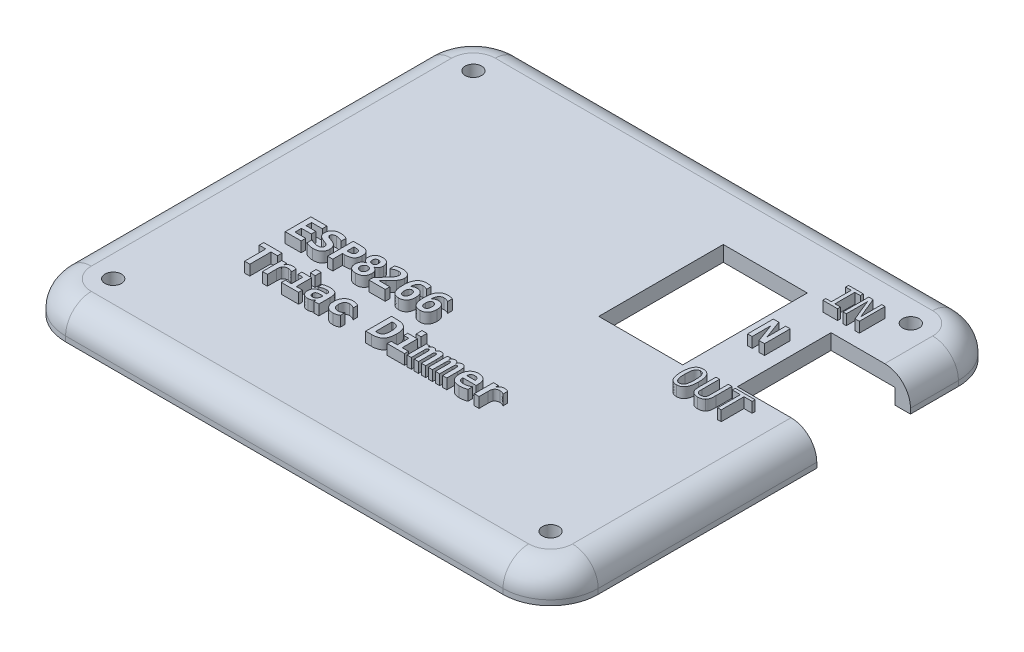
SolidWorks part; units mm, degrees
ref_plane "Front Plane" through (0, 0, 0) normal (0, 0, 1) x (1, 0, 0)
ref_plane "Top Plane" through (0, 0, 0) normal (0, 1, 0) x (1, 0, 0)
ref_plane "Right Plane" through (0, 0, 0) normal (1, 0, 0) x (0, 0, -1)
sketch "Sketch1" plane through (0, 0, 0) normal (0, 1, 0) x (1, 0, 0)
  line L0 (-3, 3) -> (-88, 3)
  line L1 (-3, 0) -> (-88, 0)
  line L2 (0, -3) -> (0, -73)
  line L3 (-3, -76) -> (-88, -76)
  line L4 (-91, -3) -> (-91, -73)
  line L5 (-94, -3) -> (-94, -73)
  line L6 (-3, -79) -> (-88, -79)
  line L7 (3, -3) -> (3, -73)
  line L8 (-3, 3.25) -> (-88, 3.25)
  line L9 (-94.25, -3) -> (-94.25, -73)
  line L10 (-3, -79.25) -> (-88, -79.25)
  line L11 (3.25, -3) -> (3.25, -73)
  line L12 (-3, 6.25) -> (-88, 6.25)
  line L13 (-97.25, -3) -> (-97.25, -73)
  line L14 (-3, -82.25) -> (-88, -82.25)
  line L15 (6.25, -3) -> (6.25, -73)
  circle A0 centre (-3.99, -9.5) radius 1.25
  circle A1 centre (-50.53, -9.5) radius 1.25
  circle A2 centre (-3.99, -31) radius 1.25
  circle A3 centre (-50.53, -31) radius 1.25
  arc A4 (0, -73) -> (-3, -76) centre (-3, -73) cw
  arc A5 (-88, -76) -> (-91, -73) centre (-88, -73) cw
  arc A6 (-88, 0) -> (-91, -3) centre (-88, -3) ccw
  arc A7 (-3, 0) -> (0, -3) centre (-3, -3) cw
  circle A8 centre (-3.99, -9.5) radius 3.25
  circle A9 centre (-3.99, -31) radius 3.25
  circle A10 centre (-50.53, -31) radius 3.25
  circle A11 centre (-50.53, -9.5) radius 3.25
  circle A12 centre (-3, -3) radius 1.6
  circle A13 centre (-88, -3) radius 1.6
  circle A14 centre (-88, -73) radius 1.6
  circle A15 centre (-3, -73) radius 1.6
  arc A20 (-88, 3) -> (-94, -3) centre (-88, -3) ccw
  arc A21 (-88, -79) -> (-94, -73) centre (-88, -73) cw
  arc A22 (3, -73) -> (-3, -79) centre (-3, -73) cw
  arc A23 (-3, 3) -> (3, -3) centre (-3, -3) cw
  arc A24 (-88, 3.25) -> (-94.25, -3) centre (-88, -3) ccw
  arc A25 (-88, -79.25) -> (-94.25, -73) centre (-88, -73) cw
  arc A26 (3.25, -73) -> (-3, -79.25) centre (-3, -73) cw
  arc A27 (-3, 3.25) -> (3.25, -3) centre (-3, -3) cw
  arc A28 (-88, 6.25) -> (-97.25, -3) centre (-88, -3) ccw
  arc A29 (-88, -82.25) -> (-97.25, -73) centre (-88, -73) cw
  arc A30 (6.25, -73) -> (-3, -82.25) centre (-3, -73) cw
  arc A31 (-3, 6.25) -> (6.25, -3) centre (-3, -3) cw
  point P21 (0, -76)
  point P26 (-91, 0)
  point P29 (0, 0)
  dimension "D1" = 2.5
  dimension "D2" = 2.5
  dimension "D3" = 2.5
  dimension "D4" = 2.5
  dimension "D11" = 3
  dimension "D13" = 3.2
  dimension "D14" = 3.2
  dimension "D15" = 3.2
  dimension "D16" = 3.2
  dimension "D5" = 21.5
  dimension "D6" = 46.54
  dimension "D7" = 9.5
  dimension "D8" = 3.99
  dimension "D9" = 76
  dimension "D10" = 91
  dimension "D18" = 3
  dimension "D12" = 2
  dimension "D19" = 0.25
  dimension "D20" = 3
extrude "Boss-Extrude1" add sketch "Sketch1" along normal blind 3 contours L12 A28 L13 A29 L14 A30 L15 A31
extrude "Boss-Extrude2" add sketch "Sketch1<7>" against normal blind 3 contours A31 L12 A28 L13 A29 L14 A30 L15 L8 A27 L11 A26 L10 A25 L9 A24 region at (2.5778, 0, -2.5778)
sketch "Sketch1<7>" plane through (0, 0, 0) normal (0, 1, 0) x (1, 0, 0) same geometry as "Sketch1"
extrude "Cut-Extrude3" cut sketch "Sketch1<8>" along normal through all contours A12 | A15 | A14 | A13
sketch "Sketch1<8>" plane through (0, 0, 0) normal (0, 1, 0) x (1, 0, 0) same geometry as "Sketch1"
sketch "Sketch2" plane through (6.25, 0, 0) normal (1, 0, 0) x (0, 0, -1)
  line L0 (-3, 3) -> (-73, 3) construction
  line L1 (-12.32, 3) -> (-30.52, 3)
  line L2 (-12.32, 3) -> (-12.32, -3)
  line L3 (-12.32, -3) -> (-30.52, -3)
  line L4 (-30.52, 3) -> (-30.52, -3)
  line L5 (-3, -3) -> (-73, -3) construction
  line L6 (-3, 3) -> (-3, -3) construction
  dimension "D1" = 18.2
  dimension "D2" = 9.32
extrude "Cut-Extrude4" cut sketch "Sketch2" against normal blind 15.43
sketch "Sketch3" plane through (0, 3, 0) normal (0, 1, 0) x (1, 0, 0)
  line L0 (6.25, -3) -> (6.25, -12.32) construction
  line L1 (-18.17, -7.95) -> (-34.49, -7.95)
  line L2 (-18.17, -7.95) -> (-18.17, -32.15)
  line L3 (-18.17, -32.15) -> (-34.49, -32.15)
  line L4 (-34.49, -7.95) -> (-34.49, -32.15)
  line L5 (-3, 6.25) -> (-88, 6.25) construction
  dimension "D1" = 24.42
  dimension "D2" = 16.32
  dimension "D3" = 14.2
  dimension "D4" = 24.2
extrude "Cut-Extrude5" cut sketch "Sketch3" against normal up to next
fillet "Fillet1" radius 5 9 edges at (6.25, 3, 51.76) (3.5407, 3, 79.5407) (-45.5, 3, 82.25) (-94.5407, 3, 79.5407) (-97.25, 3, 38) (-94.5407, 3, -3.5407) (-45.5, 3, -6.25) (3.5407, 3, -3.5407) (6.25, 3, 7.66)
sketch "Sketch4" plane through (0, 3, 0) normal (0, 1, 0) x (1, 0, 0)
  text T0 "IN" font "DejaVu Sans Mono" height 5
  text T1 "<b>N</b>" font "DejaVu Sans Mono" height 5
  text T2 "OUT" font "DejaVu Sans Mono" height 5
  text T3 "<b>ESP8266 </b>\r\n<b>Triac Dimmer</b>" font "DejaVu Sans Mono" height 5
  point P1 (0, 0)
  point P4 (-14.0611, -9.6592)
extrude "Boss-Extrude3" add sketch "Sketch4" along normal blind 2
